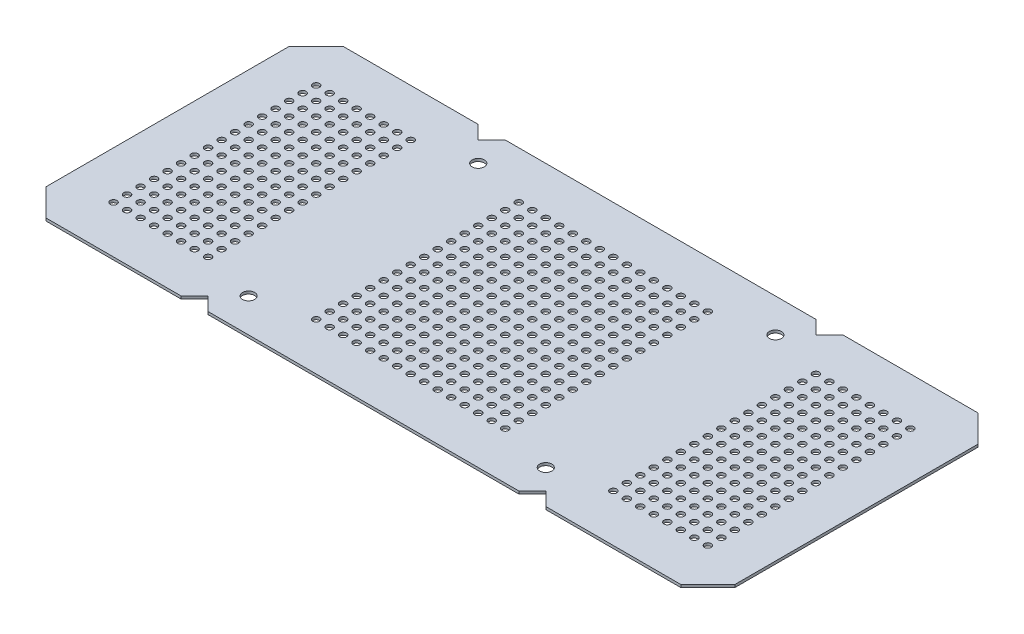
SolidWorks part; units mm, degrees
ref_plane "Alzado" through (0, 0, 0) normal (0, 0, 1) x (1, 0, 0)
ref_plane "Planta" through (0, 0, 0) normal (0, 1, 0) x (1, 0, 0)
ref_plane "Vista lateral" through (0, 0, 0) normal (1, 0, 0) x (0, 0, -1)
sketch "Croquis1" plane through (0, 0, 0) normal (0, 1, 0) x (1, 0, 0)
  line L13 (-145, 80) -> (-225, 80)
  line L14 (-225, 80) -> (-225, -80)
  line L15 (-225, -80) -> (-145, -80)
  line L16 (-145, 80) -> (-145, -80)
  line L17 (225, 80) -> (145, 80)
  line L18 (145, 80) -> (145, -80)
  line L19 (145, -80) -> (225, -80)
  line L20 (225, 80) -> (225, -80)
  line L25 (-125, 100) -> (-125, -100) construction
  line L26 (125, 100) -> (125, -100) construction
  line L51 (-245, 100) -> (-245, -100) construction
  line L52 (245, -100) -> (245, 100) construction
  line L53 (-245, 100) -> (-125, 100) construction
  line L54 (-245, -100) -> (-125, -100) construction
  line L55 (-125, 100) -> (125, 100) construction
  line L56 (125, 100) -> (245, 100) construction
  line L57 (-125, -100) -> (125, -100) construction
  line L58 (125, -100) -> (245, -100) construction
  line L59 (-245, 100) -> (-235, 110)
  line L60 (-235, 110) -> (-135, 110)
  line L61 (-135, 110) -> (-125, 100)
  line L62 (-125, 100) -> (-115, 110)
  line L63 (-115, 110) -> (115, 110)
  line L64 (115, 110) -> (125, 100)
  line L65 (125, 100) -> (135, 110)
  line L66 (135, 110) -> (235, 110)
  line L67 (235, 110) -> (245, 100)
  line L68 (-245, 100) -> (-255, 90)
  line L69 (-255, 90) -> (-255, -90)
  line L70 (-255, -90) -> (-245, -100)
  line L71 (245, 100) -> (255, 90)
  line L72 (255, 90) -> (255, -90)
  line L73 (255, -90) -> (245, -100)
  line L74 (-245, -100) -> (-235, -110)
  line L75 (-235, -110) -> (-135, -110)
  line L76 (-135, -110) -> (-125, -100)
  line L77 (-125, -100) -> (-115, -110)
  line L78 (-115, -110) -> (115, -110)
  line L79 (115, -110) -> (125, -100)
  line L80 (125, -100) -> (135, -110)
  line L81 (135, -110) -> (235, -110)
  line L82 (235, -110) -> (245, -100)
  line L83 (-75, 80) -> (-75, -80)
  line L84 (-75, -80) -> (75, -80)
  line L85 (75, -80) -> (75, 80)
  line L86 (75, 80) -> (-75, 80)
  circle A0 centre (-110, 85) radius 4.5
  circle A1 centre (110, 85) radius 4.5
  circle A2 centre (110, -85) radius 4.5
  circle A3 centre (-110, -85) radius 4.5
  circle A4 centre (-110, 85) radius 25 construction
  point P16 (0, 100)
  point P17 (-225, 0)
  point P48 (-75, 0)
  dimension "D30" = 50
  dimension "D31" = 9
  dimension "D1" = 120
  dimension "D2" = 200
  dimension "D3" = 250
  dimension "D4" = 120
  dimension "D5" = 20
  dimension "D6" = 20
  dimension "D7" = 10
  dimension "D8" = 20
  dimension "D9" = 45
  dimension "D10" = 45
  dimension "D11" = 10
  dimension "D12" = 20
  dimension "D13" = 45
  dimension "D14" = 45
  dimension "D15" = 45
  dimension "D16" = 45
  dimension "D17" = 10
  dimension "D18" = 45
  dimension "D19" = 45
  dimension "D20" = 10
  dimension "D21" = 45
  dimension "D22" = 10
  dimension "D23" = 10
  dimension "D24" = 10
  dimension "D25" = 10
  dimension "D26" = 50
  dimension "D27" = 50
  dimension "D28" = 30
  dimension "D29" = 30
  dimension "D32" = 15
  dimension "D33" = 15
  dimension "D34" = 15
  dimension "D35" = 15
  dimension "D36" = 15
  dimension "D37" = 15
extrude "Saliente-Extruir1" add sketch "Croquis1" along normal blind 2
sketch "Croquis4" plane through (0, 2, 0) normal (0, 1, 0) x (1, 0, 0)
  line L0 (-225, 80) -> (-225, -80)
  line L1 (-225, -80) -> (-145, -80)
  line L2 (-145, -80) -> (-145, 80)
  line L3 (-145, 80) -> (-225, 80)
  line L4 (-75, 80) -> (75, 80)
  line L5 (75, 80) -> (75, -80)
  line L6 (75, -80) -> (-75, -80)
  line L7 (-75, -80) -> (-75, 80)
  line L8 (145, 80) -> (145, -80)
  line L9 (145, -80) -> (225, -80)
  line L10 (225, -80) -> (225, 80)
  line L11 (225, 80) -> (145, 80)
  circle A0 centre (-220, 75) radius 2.5
  circle A1 centre (-210, 75) radius 2.5
  circle A2 centre (-200, 75) radius 2.5
  circle A3 centre (-190, 75) radius 2.5
  circle A4 centre (-180, 75) radius 2.5
  circle A5 centre (-170, 75) radius 2.5
  circle A6 centre (-160, 75) radius 2.5
  circle A7 centre (-150, 75) radius 2.5
  circle A8 centre (-210, 65) radius 2.5
  circle A9 centre (-200, 65) radius 2.5
  circle A10 centre (-190, 65) radius 2.5
  circle A11 centre (-180, 65) radius 2.5
  circle A12 centre (-170, 65) radius 2.5
  circle A13 centre (-160, 65) radius 2.5
  circle A14 centre (-150, 65) radius 2.5
  circle A15 centre (-210, 55) radius 2.5
  circle A16 centre (-200, 55) radius 2.5
  circle A17 centre (-190, 55) radius 2.5
  circle A18 centre (-180, 55) radius 2.5
  circle A19 centre (-170, 55) radius 2.5
  circle A20 centre (-160, 55) radius 2.5
  circle A21 centre (-150, 55) radius 2.5
  circle A22 centre (-210, 45) radius 2.5
  circle A23 centre (-200, 45) radius 2.5
  circle A24 centre (-190, 45) radius 2.5
  circle A25 centre (-180, 45) radius 2.5
  circle A26 centre (-170, 45) radius 2.5
  circle A27 centre (-160, 45) radius 2.5
  circle A28 centre (-150, 45) radius 2.5
  circle A29 centre (-210, 35) radius 2.5
  circle A30 centre (-200, 35) radius 2.5
  circle A31 centre (-190, 35) radius 2.5
  circle A32 centre (-180, 35) radius 2.5
  circle A33 centre (-170, 35) radius 2.5
  circle A34 centre (-160, 35) radius 2.5
  circle A35 centre (-150, 35) radius 2.5
  circle A36 centre (-210, 25) radius 2.5
  circle A37 centre (-200, 25) radius 2.5
  circle A38 centre (-190, 25) radius 2.5
  circle A39 centre (-180, 25) radius 2.5
  circle A40 centre (-170, 25) radius 2.5
  circle A41 centre (-160, 25) radius 2.5
  circle A42 centre (-150, 25) radius 2.5
  circle A43 centre (-210, 15) radius 2.5
  circle A44 centre (-200, 15) radius 2.5
  circle A45 centre (-190, 15) radius 2.5
  circle A46 centre (-180, 15) radius 2.5
  circle A47 centre (-170, 15) radius 2.5
  circle A48 centre (-160, 15) radius 2.5
  circle A49 centre (-150, 15) radius 2.5
  circle A50 centre (-210, 5) radius 2.5
  circle A51 centre (-200, 5) radius 2.5
  circle A52 centre (-190, 5) radius 2.5
  circle A53 centre (-180, 5) radius 2.5
  circle A54 centre (-170, 5) radius 2.5
  circle A55 centre (-160, 5) radius 2.5
  circle A56 centre (-150, 5) radius 2.5
  circle A57 centre (-210, -5) radius 2.5
  circle A58 centre (-200, -5) radius 2.5
  circle A59 centre (-190, -5) radius 2.5
  circle A60 centre (-180, -5) radius 2.5
  circle A61 centre (-170, -5) radius 2.5
  circle A62 centre (-160, -5) radius 2.5
  circle A63 centre (-150, -5) radius 2.5
  circle A64 centre (-210, -15) radius 2.5
  circle A65 centre (-200, -15) radius 2.5
  circle A66 centre (-190, -15) radius 2.5
  circle A67 centre (-180, -15) radius 2.5
  circle A68 centre (-170, -15) radius 2.5
  circle A69 centre (-160, -15) radius 2.5
  circle A70 centre (-150, -15) radius 2.5
  circle A71 centre (-210, -25) radius 2.5
  circle A72 centre (-200, -25) radius 2.5
  circle A73 centre (-190, -25) radius 2.5
  circle A74 centre (-180, -25) radius 2.5
  circle A75 centre (-170, -25) radius 2.5
  circle A76 centre (-160, -25) radius 2.5
  circle A77 centre (-150, -25) radius 2.5
  circle A78 centre (-210, -35) radius 2.5
  circle A79 centre (-200, -35) radius 2.5
  circle A80 centre (-190, -35) radius 2.5
  circle A81 centre (-180, -35) radius 2.5
  circle A82 centre (-170, -35) radius 2.5
  circle A83 centre (-160, -35) radius 2.5
  circle A84 centre (-150, -35) radius 2.5
  circle A85 centre (-210, -45) radius 2.5
  circle A86 centre (-200, -45) radius 2.5
  circle A87 centre (-190, -45) radius 2.5
  circle A88 centre (-180, -45) radius 2.5
  circle A89 centre (-170, -45) radius 2.5
  circle A90 centre (-160, -45) radius 2.5
  circle A91 centre (-150, -45) radius 2.5
  circle A92 centre (-210, -55) radius 2.5
  circle A93 centre (-200, -55) radius 2.5
  circle A94 centre (-190, -55) radius 2.5
  circle A95 centre (-180, -55) radius 2.5
  circle A96 centre (-170, -55) radius 2.5
  circle A97 centre (-160, -55) radius 2.5
  circle A98 centre (-150, -55) radius 2.5
  circle A99 centre (-210, -65) radius 2.5
  circle A100 centre (-200, -65) radius 2.5
  circle A101 centre (-190, -65) radius 2.5
  circle A102 centre (-180, -65) radius 2.5
  circle A103 centre (-170, -65) radius 2.5
  circle A104 centre (-160, -65) radius 2.5
  circle A105 centre (-150, -65) radius 2.5
  circle A106 centre (-210, -75) radius 2.5
  circle A107 centre (-200, -75) radius 2.5
  circle A108 centre (-190, -75) radius 2.5
  circle A109 centre (-180, -75) radius 2.5
  circle A110 centre (-170, -75) radius 2.5
  circle A111 centre (-160, -75) radius 2.5
  circle A112 centre (-150, -75) radius 2.5
  circle A113 centre (-220, 65) radius 2.5
  circle A114 centre (-220, 55) radius 2.5
  circle A115 centre (-220, 45) radius 2.5
  circle A116 centre (-220, 35) radius 2.5
  circle A117 centre (-220, 25) radius 2.5
  circle A118 centre (-220, 15) radius 2.5
  circle A119 centre (-220, 5) radius 2.5
  circle A120 centre (-220, -5) radius 2.5
  circle A121 centre (-220, -15) radius 2.5
  circle A122 centre (-220, -25) radius 2.5
  circle A123 centre (-220, -35) radius 2.5
  circle A124 centre (-220, -45) radius 2.5
  circle A125 centre (-220, -55) radius 2.5
  circle A126 centre (-220, -65) radius 2.5
  circle A127 centre (-220, -75) radius 2.5
  circle A128 centre (150, 75) radius 2.5
  circle A129 centre (160, 75) radius 2.5
  circle A130 centre (170, 75) radius 2.5
  circle A131 centre (180, 75) radius 2.5
  circle A132 centre (190, 75) radius 2.5
  circle A133 centre (200, 75) radius 2.5
  circle A134 centre (210, 75) radius 2.5
  circle A135 centre (220, 75) radius 2.5
  circle A136 centre (160, 65) radius 2.5
  circle A137 centre (170, 65) radius 2.5
  circle A138 centre (180, 65) radius 2.5
  circle A139 centre (190, 65) radius 2.5
  circle A140 centre (200, 65) radius 2.5
  circle A141 centre (210, 65) radius 2.5
  circle A142 centre (220, 65) radius 2.5
  circle A143 centre (160, 55) radius 2.5
  circle A144 centre (170, 55) radius 2.5
  circle A145 centre (180, 55) radius 2.5
  circle A146 centre (190, 55) radius 2.5
  circle A147 centre (200, 55) radius 2.5
  circle A148 centre (210, 55) radius 2.5
  circle A149 centre (220, 55) radius 2.5
  circle A150 centre (160, 45) radius 2.5
  circle A151 centre (170, 45) radius 2.5
  circle A152 centre (180, 45) radius 2.5
  circle A153 centre (190, 45) radius 2.5
  circle A154 centre (200, 45) radius 2.5
  circle A155 centre (210, 45) radius 2.5
  circle A156 centre (220, 45) radius 2.5
  circle A157 centre (160, 35) radius 2.5
  circle A158 centre (170, 35) radius 2.5
  circle A159 centre (180, 35) radius 2.5
  circle A160 centre (190, 35) radius 2.5
  circle A161 centre (200, 35) radius 2.5
  circle A162 centre (210, 35) radius 2.5
  circle A163 centre (220, 35) radius 2.5
  circle A164 centre (160, 25) radius 2.5
  circle A165 centre (170, 25) radius 2.5
  circle A166 centre (180, 25) radius 2.5
  circle A167 centre (190, 25) radius 2.5
  circle A168 centre (200, 25) radius 2.5
  circle A169 centre (210, 25) radius 2.5
  circle A170 centre (220, 25) radius 2.5
  circle A171 centre (160, 15) radius 2.5
  circle A172 centre (170, 15) radius 2.5
  circle A173 centre (180, 15) radius 2.5
  circle A174 centre (190, 15) radius 2.5
  circle A175 centre (200, 15) radius 2.5
  circle A176 centre (210, 15) radius 2.5
  circle A177 centre (220, 15) radius 2.5
  circle A178 centre (160, 5) radius 2.5
  circle A179 centre (170, 5) radius 2.5
  circle A180 centre (180, 5) radius 2.5
  circle A181 centre (190, 5) radius 2.5
  circle A182 centre (200, 5) radius 2.5
  circle A183 centre (210, 5) radius 2.5
  circle A184 centre (220, 5) radius 2.5
  circle A185 centre (160, -5) radius 2.5
  circle A186 centre (170, -5) radius 2.5
  circle A187 centre (180, -5) radius 2.5
  circle A188 centre (190, -5) radius 2.5
  circle A189 centre (200, -5) radius 2.5
  circle A190 centre (210, -5) radius 2.5
  circle A191 centre (220, -5) radius 2.5
  circle A192 centre (160, -15) radius 2.5
  circle A193 centre (170, -15) radius 2.5
  circle A194 centre (180, -15) radius 2.5
  circle A195 centre (190, -15) radius 2.5
  circle A196 centre (200, -15) radius 2.5
  circle A197 centre (210, -15) radius 2.5
  circle A198 centre (220, -15) radius 2.5
  circle A199 centre (160, -25) radius 2.5
  circle A200 centre (170, -25) radius 2.5
  circle A201 centre (180, -25) radius 2.5
  circle A202 centre (190, -25) radius 2.5
  circle A203 centre (200, -25) radius 2.5
  circle A204 centre (210, -25) radius 2.5
  circle A205 centre (220, -25) radius 2.5
  circle A206 centre (160, -35) radius 2.5
  circle A207 centre (170, -35) radius 2.5
  circle A208 centre (180, -35) radius 2.5
  circle A209 centre (190, -35) radius 2.5
  circle A210 centre (200, -35) radius 2.5
  circle A211 centre (210, -35) radius 2.5
  circle A212 centre (220, -35) radius 2.5
  circle A213 centre (160, -45) radius 2.5
  circle A214 centre (170, -45) radius 2.5
  circle A215 centre (180, -45) radius 2.5
  circle A216 centre (190, -45) radius 2.5
  circle A217 centre (200, -45) radius 2.5
  circle A218 centre (210, -45) radius 2.5
  circle A219 centre (220, -45) radius 2.5
  circle A220 centre (160, -55) radius 2.5
  circle A221 centre (170, -55) radius 2.5
  circle A222 centre (180, -55) radius 2.5
  circle A223 centre (190, -55) radius 2.5
  circle A224 centre (200, -55) radius 2.5
  circle A225 centre (210, -55) radius 2.5
  circle A226 centre (220, -55) radius 2.5
  circle A227 centre (160, -65) radius 2.5
  circle A228 centre (170, -65) radius 2.5
  circle A229 centre (180, -65) radius 2.5
  circle A230 centre (190, -65) radius 2.5
  circle A231 centre (200, -65) radius 2.5
  circle A232 centre (210, -65) radius 2.5
  circle A233 centre (220, -65) radius 2.5
  circle A234 centre (160, -75) radius 2.5
  circle A235 centre (170, -75) radius 2.5
  circle A236 centre (180, -75) radius 2.5
  circle A237 centre (190, -75) radius 2.5
  circle A238 centre (200, -75) radius 2.5
  circle A239 centre (210, -75) radius 2.5
  circle A240 centre (220, -75) radius 2.5
  circle A241 centre (150, 65) radius 2.5
  circle A242 centre (150, 55) radius 2.5
  circle A243 centre (150, 45) radius 2.5
  circle A244 centre (150, 35) radius 2.5
  circle A245 centre (150, 25) radius 2.5
  circle A246 centre (150, 15) radius 2.5
  circle A247 centre (150, 5) radius 2.5
  circle A248 centre (150, -5) radius 2.5
  circle A249 centre (150, -15) radius 2.5
  circle A250 centre (150, -25) radius 2.5
  circle A251 centre (150, -35) radius 2.5
  circle A252 centre (150, -45) radius 2.5
  circle A253 centre (150, -55) radius 2.5
  circle A254 centre (150, -65) radius 2.5
  circle A255 centre (150, -75) radius 2.5
  circle A256 centre (-70, 75) radius 2.5
  circle A257 centre (-60, 75) radius 2.5
  circle A258 centre (-50, 75) radius 2.5
  circle A259 centre (-40, 75) radius 2.5
  circle A260 centre (-30, 75) radius 2.5
  circle A261 centre (-20, 75) radius 2.5
  circle A262 centre (-10, 75) radius 2.5
  circle A263 centre (0, 75) radius 2.5
  circle A264 centre (10, 75) radius 2.5
  circle A265 centre (20, 75) radius 2.5
  circle A266 centre (30, 75) radius 2.5
  circle A267 centre (40, 75) radius 2.5
  circle A268 centre (50, 75) radius 2.5
  circle A269 centre (60, 75) radius 2.5
  circle A270 centre (70, 75) radius 2.5
  circle A271 centre (-60, 65) radius 2.5
  circle A272 centre (-50, 65) radius 2.5
  circle A273 centre (-40, 65) radius 2.5
  circle A274 centre (-30, 65) radius 2.5
  circle A275 centre (-20, 65) radius 2.5
  circle A276 centre (-10, 65) radius 2.5
  circle A277 centre (0, 65) radius 2.5
  circle A278 centre (10, 65) radius 2.5
  circle A279 centre (20, 65) radius 2.5
  circle A280 centre (30, 65) radius 2.5
  circle A281 centre (40, 65) radius 2.5
  circle A282 centre (50, 65) radius 2.5
  circle A283 centre (60, 65) radius 2.5
  circle A284 centre (70, 65) radius 2.5
  circle A285 centre (-60, 55) radius 2.5
  circle A286 centre (-50, 55) radius 2.5
  circle A287 centre (-40, 55) radius 2.5
  circle A288 centre (-30, 55) radius 2.5
  circle A289 centre (-20, 55) radius 2.5
  circle A290 centre (-10, 55) radius 2.5
  circle A291 centre (0, 55) radius 2.5
  circle A292 centre (10, 55) radius 2.5
  circle A293 centre (20, 55) radius 2.5
  circle A294 centre (30, 55) radius 2.5
  circle A295 centre (40, 55) radius 2.5
  circle A296 centre (50, 55) radius 2.5
  circle A297 centre (60, 55) radius 2.5
  circle A298 centre (70, 55) radius 2.5
  circle A299 centre (-60, 45) radius 2.5
  circle A300 centre (-50, 45) radius 2.5
  circle A301 centre (-40, 45) radius 2.5
  circle A302 centre (-30, 45) radius 2.5
  circle A303 centre (-20, 45) radius 2.5
  circle A304 centre (-10, 45) radius 2.5
  circle A305 centre (0, 45) radius 2.5
  circle A306 centre (10, 45) radius 2.5
  circle A307 centre (20, 45) radius 2.5
  circle A308 centre (30, 45) radius 2.5
  circle A309 centre (40, 45) radius 2.5
  circle A310 centre (50, 45) radius 2.5
  circle A311 centre (60, 45) radius 2.5
  circle A312 centre (70, 45) radius 2.5
  circle A313 centre (-60, 35) radius 2.5
  circle A314 centre (-50, 35) radius 2.5
  circle A315 centre (-40, 35) radius 2.5
  circle A316 centre (-30, 35) radius 2.5
  circle A317 centre (-20, 35) radius 2.5
  circle A318 centre (-10, 35) radius 2.5
  circle A319 centre (0, 35) radius 2.5
  circle A320 centre (10, 35) radius 2.5
  circle A321 centre (20, 35) radius 2.5
  circle A322 centre (30, 35) radius 2.5
  circle A323 centre (40, 35) radius 2.5
  circle A324 centre (50, 35) radius 2.5
  circle A325 centre (60, 35) radius 2.5
  circle A326 centre (70, 35) radius 2.5
  circle A327 centre (-60, 25) radius 2.5
  circle A328 centre (-50, 25) radius 2.5
  circle A329 centre (-40, 25) radius 2.5
  circle A330 centre (-30, 25) radius 2.5
  circle A331 centre (-20, 25) radius 2.5
  circle A332 centre (-10, 25) radius 2.5
  circle A333 centre (0, 25) radius 2.5
  circle A334 centre (10, 25) radius 2.5
  circle A335 centre (20, 25) radius 2.5
  circle A336 centre (30, 25) radius 2.5
  circle A337 centre (40, 25) radius 2.5
  circle A338 centre (50, 25) radius 2.5
  circle A339 centre (60, 25) radius 2.5
  circle A340 centre (70, 25) radius 2.5
  circle A341 centre (-60, 15) radius 2.5
  circle A342 centre (-50, 15) radius 2.5
  circle A343 centre (-40, 15) radius 2.5
  circle A344 centre (-30, 15) radius 2.5
  circle A345 centre (-20, 15) radius 2.5
  circle A346 centre (-10, 15) radius 2.5
  circle A347 centre (0, 15) radius 2.5
  circle A348 centre (10, 15) radius 2.5
  circle A349 centre (20, 15) radius 2.5
  circle A350 centre (30, 15) radius 2.5
  circle A351 centre (40, 15) radius 2.5
  circle A352 centre (50, 15) radius 2.5
  circle A353 centre (60, 15) radius 2.5
  circle A354 centre (70, 15) radius 2.5
  circle A355 centre (-60, 5) radius 2.5
  circle A356 centre (-50, 5) radius 2.5
  circle A357 centre (-40, 5) radius 2.5
  circle A358 centre (-30, 5) radius 2.5
  circle A359 centre (-20, 5) radius 2.5
  circle A360 centre (-10, 5) radius 2.5
  circle A361 centre (0, 5) radius 2.5
  circle A362 centre (10, 5) radius 2.5
  circle A363 centre (20, 5) radius 2.5
  circle A364 centre (30, 5) radius 2.5
  circle A365 centre (40, 5) radius 2.5
  circle A366 centre (50, 5) radius 2.5
  circle A367 centre (60, 5) radius 2.5
  circle A368 centre (70, 5) radius 2.5
  circle A369 centre (-60, -5) radius 2.5
  circle A370 centre (-50, -5) radius 2.5
  circle A371 centre (-40, -5) radius 2.5
  circle A372 centre (-30, -5) radius 2.5
  circle A373 centre (-20, -5) radius 2.5
  circle A374 centre (-10, -5) radius 2.5
  circle A375 centre (0, -5) radius 2.5
  circle A376 centre (10, -5) radius 2.5
  circle A377 centre (20, -5) radius 2.5
  circle A378 centre (30, -5) radius 2.5
  circle A379 centre (40, -5) radius 2.5
  circle A380 centre (50, -5) radius 2.5
  circle A381 centre (60, -5) radius 2.5
  circle A382 centre (70, -5) radius 2.5
  circle A383 centre (-60, -15) radius 2.5
  circle A384 centre (-50, -15) radius 2.5
  circle A385 centre (-40, -15) radius 2.5
  circle A386 centre (-30, -15) radius 2.5
  circle A387 centre (-20, -15) radius 2.5
  circle A388 centre (-10, -15) radius 2.5
  circle A389 centre (0, -15) radius 2.5
  circle A390 centre (10, -15) radius 2.5
  circle A391 centre (20, -15) radius 2.5
  circle A392 centre (30, -15) radius 2.5
  circle A393 centre (40, -15) radius 2.5
  circle A394 centre (50, -15) radius 2.5
  circle A395 centre (60, -15) radius 2.5
  circle A396 centre (70, -15) radius 2.5
  circle A397 centre (-60, -25) radius 2.5
  circle A398 centre (-50, -25) radius 2.5
  circle A399 centre (-40, -25) radius 2.5
  circle A400 centre (-30, -25) radius 2.5
  circle A401 centre (-20, -25) radius 2.5
  circle A402 centre (-10, -25) radius 2.5
  circle A403 centre (0, -25) radius 2.5
  circle A404 centre (10, -25) radius 2.5
  circle A405 centre (20, -25) radius 2.5
  circle A406 centre (30, -25) radius 2.5
  circle A407 centre (40, -25) radius 2.5
  circle A408 centre (50, -25) radius 2.5
  circle A409 centre (60, -25) radius 2.5
  circle A410 centre (70, -25) radius 2.5
  circle A411 centre (-60, -35) radius 2.5
  circle A412 centre (-50, -35) radius 2.5
  circle A413 centre (-40, -35) radius 2.5
  circle A414 centre (-30, -35) radius 2.5
  circle A415 centre (-20, -35) radius 2.5
  circle A416 centre (-10, -35) radius 2.5
  circle A417 centre (0, -35) radius 2.5
  circle A418 centre (10, -35) radius 2.5
  circle A419 centre (20, -35) radius 2.5
  circle A420 centre (30, -35) radius 2.5
  circle A421 centre (40, -35) radius 2.5
  circle A422 centre (50, -35) radius 2.5
  circle A423 centre (60, -35) radius 2.5
  circle A424 centre (70, -35) radius 2.5
  circle A425 centre (-60, -45) radius 2.5
  circle A426 centre (-50, -45) radius 2.5
  circle A427 centre (-40, -45) radius 2.5
  circle A428 centre (-30, -45) radius 2.5
  circle A429 centre (-20, -45) radius 2.5
  circle A430 centre (-10, -45) radius 2.5
  circle A431 centre (0, -45) radius 2.5
  circle A432 centre (10, -45) radius 2.5
  circle A433 centre (20, -45) radius 2.5
  circle A434 centre (30, -45) radius 2.5
  circle A435 centre (40, -45) radius 2.5
  circle A436 centre (50, -45) radius 2.5
  circle A437 centre (60, -45) radius 2.5
  circle A438 centre (70, -45) radius 2.5
  circle A439 centre (-60, -55) radius 2.5
  circle A440 centre (-50, -55) radius 2.5
  circle A441 centre (-40, -55) radius 2.5
  circle A442 centre (-30, -55) radius 2.5
  circle A443 centre (-20, -55) radius 2.5
  circle A444 centre (-10, -55) radius 2.5
  circle A445 centre (0, -55) radius 2.5
  circle A446 centre (10, -55) radius 2.5
  circle A447 centre (20, -55) radius 2.5
  circle A448 centre (30, -55) radius 2.5
  circle A449 centre (40, -55) radius 2.5
  circle A450 centre (50, -55) radius 2.5
  circle A451 centre (60, -55) radius 2.5
  circle A452 centre (70, -55) radius 2.5
  circle A453 centre (-60, -65) radius 2.5
  circle A454 centre (-50, -65) radius 2.5
  circle A455 centre (-40, -65) radius 2.5
  circle A456 centre (-30, -65) radius 2.5
  circle A457 centre (-20, -65) radius 2.5
  circle A458 centre (-10, -65) radius 2.5
  circle A459 centre (0, -65) radius 2.5
  circle A460 centre (10, -65) radius 2.5
  circle A461 centre (20, -65) radius 2.5
  circle A462 centre (30, -65) radius 2.5
  circle A463 centre (40, -65) radius 2.5
  circle A464 centre (50, -65) radius 2.5
  circle A465 centre (60, -65) radius 2.5
  circle A466 centre (70, -65) radius 2.5
  circle A467 centre (-60, -75) radius 2.5
  circle A468 centre (-50, -75) radius 2.5
  circle A469 centre (-40, -75) radius 2.5
  circle A470 centre (-30, -75) radius 2.5
  circle A471 centre (-20, -75) radius 2.5
  circle A472 centre (-10, -75) radius 2.5
  circle A473 centre (0, -75) radius 2.5
  circle A474 centre (10, -75) radius 2.5
  circle A475 centre (20, -75) radius 2.5
  circle A476 centre (30, -75) radius 2.5
  circle A477 centre (40, -75) radius 2.5
  circle A478 centre (50, -75) radius 2.5
  circle A479 centre (60, -75) radius 2.5
  circle A480 centre (70, -75) radius 2.5
  circle A481 centre (-70, 65) radius 2.5
  circle A482 centre (-70, 55) radius 2.5
  circle A483 centre (-70, 45) radius 2.5
  circle A484 centre (-70, 35) radius 2.5
  circle A485 centre (-70, 25) radius 2.5
  circle A486 centre (-70, 15) radius 2.5
  circle A487 centre (-70, 5) radius 2.5
  circle A488 centre (-70, -5) radius 2.5
  circle A489 centre (-70, -15) radius 2.5
  circle A490 centre (-70, -25) radius 2.5
  circle A491 centre (-70, -35) radius 2.5
  circle A492 centre (-70, -45) radius 2.5
  circle A493 centre (-70, -55) radius 2.5
  circle A494 centre (-70, -65) radius 2.5
  circle A495 centre (-70, -75) radius 2.5
  dimension "D1" = 5
  dimension "D6" = 5
  dimension "D11" = 5
  dimension "D2" = 5
  dimension "D3" = 5
  dimension "D7" = 5
  dimension "D8" = 5
  dimension "D12" = 5
  dimension "D13" = 5
  dimension "D4" = 8
  dimension "D5" = 16
  dimension "D9" = 8
  dimension "D10" = 16
  dimension "D14" = 15
  dimension "D15" = 16
extrude "Saliente-Extruir2" add sketch "Croquis4" against normal blind 2
